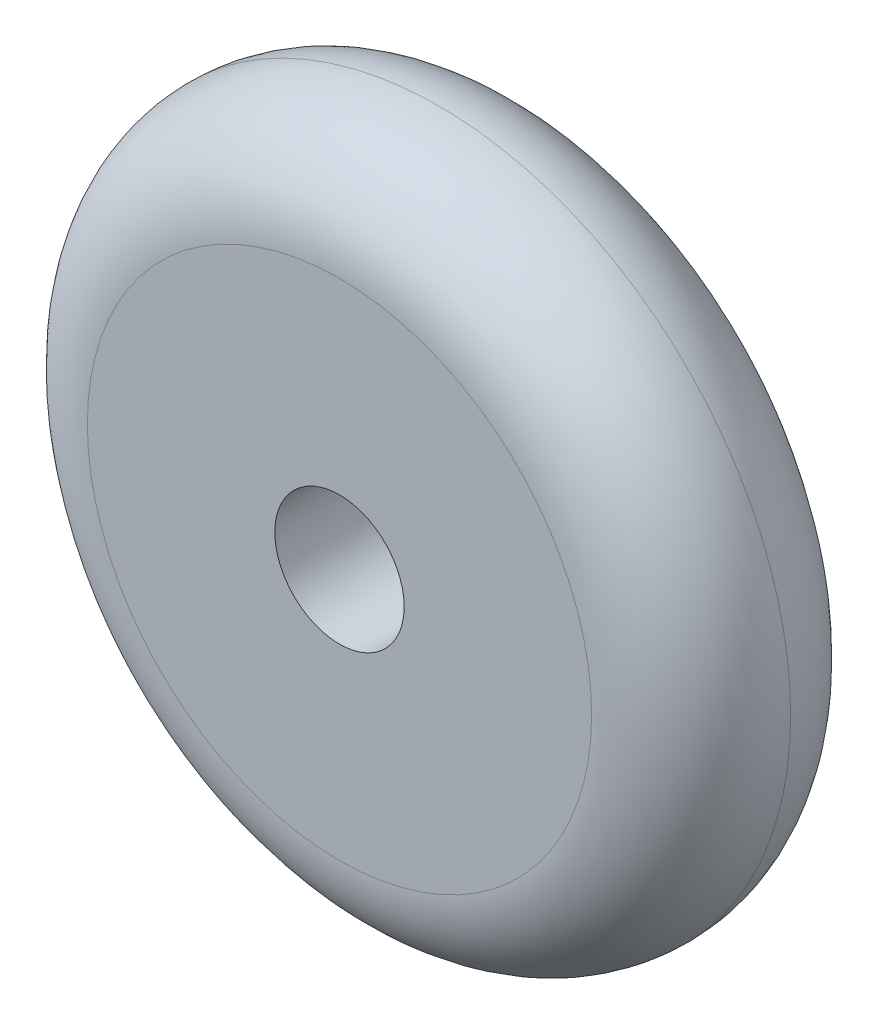
SolidWorks part; units mm, degrees
ref_plane "前基準面" through (0, 0, 0) normal (0, 0, 1) x (1, 0, 0)
ref_plane "上基準面" through (0, 0, 0) normal (0, 1, 0) x (1, 0, 0)
ref_plane "右基準面" through (0, 0, 0) normal (1, 0, 0) x (0, 0, -1)
sketch "草圖1" plane through (0, 0, 0) normal (0, 0, 1) x (1, 0, 0)
  circle A0 centre (0, 0) radius 21.2
  circle A1 centre (0, 0) radius 3.9
extrude "填料-伸長1" add sketch "草圖1" along normal blind 12 contours A0 | A1
fillet "圓角1" radius 6 1 edges at (21.2, 0, 12)
fillet "圓角2" radius 6 1 edges at (21.2, 0, 0)
